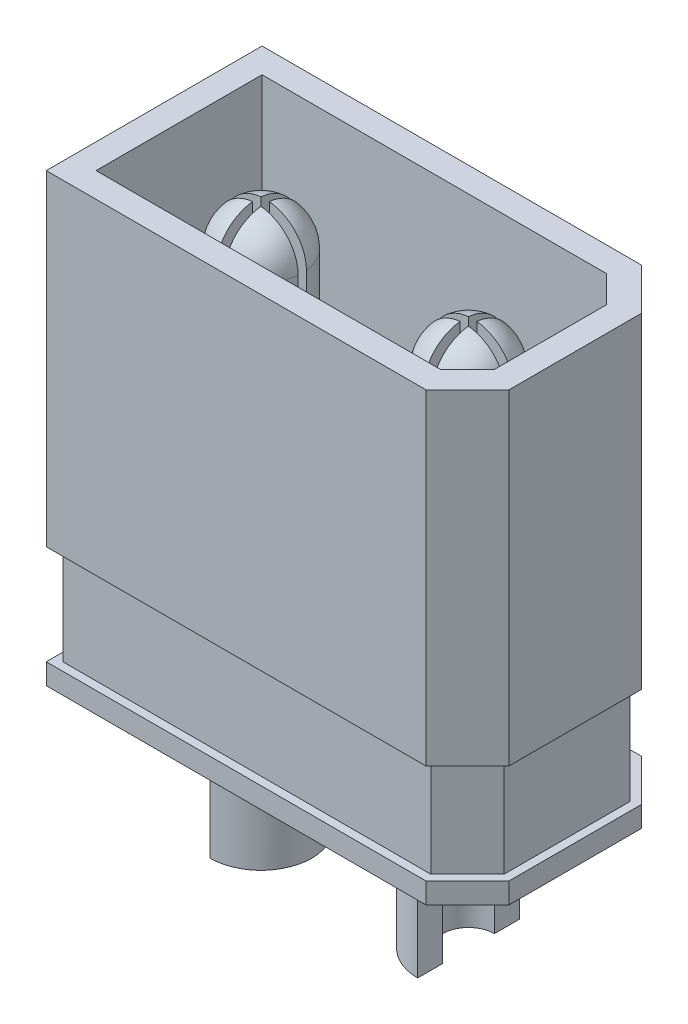
SolidWorks part; units mm, degrees
ref_plane "Front Plane" through (0, 0, 0) normal (0, 0, 1) x (1, 0, 0)
ref_plane "Top Plane" through (0, 0, 0) normal (0, 1, 0) x (1, 0, 0)
ref_plane "Right Plane" through (0, 0, 0) normal (1, 0, 0) x (0, 0, -1)
sketch "Sketch1" plane through (0, 0, 0) normal (0, 1, 0) x (1, 0, 0)
  line L0 (5.075, 1.6) -> (4.075, 2.6)
  line L1 (-5.075, 2.6) -> (5.075, 2.6)
  line L2 (-5.075, 2.6) -> (-5.075, -2.6)
  line L3 (-5.075, -2.6) -> (5.075, -2.6)
  line L4 (5.075, 2.6) -> (5.075, -2.6)
  line L5 (-5.075, 2.6) -> (5.075, -2.6) construction
  line L6 (-5.075, -2.6) -> (5.075, 2.6) construction
  line L7 (-5.075, 0) -> (5.075, 0) construction
  line L8 (5.075, -1.6) -> (4.075, -2.6)
  point P0 (0, 0)
  dimension "D1" = 5.2
  dimension "D2" = 10.15
  dimension "D3" = 1
  dimension "D4" = 45
extrude "Shape" add sketch "Sketch1" along normal blind 10.75 contours L8 L4 L0 L1 L2 L3 region at (-0.0916, 0, 0)
sketch "Sketch2" plane through (0, 10.75, 0) normal (0, 1, 0) x (1, 0, 0)
  line L12 (3.8265, -2) -> (4.475, -1.3515)
  line L13 (4.475, -1.3515) -> (4.475, 1.3515)
  line L14 (4.475, 1.3515) -> (3.8265, 2)
  line L15 (3.8265, 2) -> (-4.475, 2)
  line L16 (-4.475, 2) -> (-4.475, -2)
  line L17 (-4.475, -2) -> (3.8265, -2)
  line L18 (3.8265, -2) -> (4.475, -1.3515)
  line L19 (4.475, -1.3515) -> (4.475, 1.3515)
  line L20 (4.475, 1.3515) -> (3.8265, 2)
  line L21 (3.8265, 2) -> (-4.475, 2)
  line L22 (-4.475, 2) -> (-4.475, -2)
  line L23 (-4.475, -2) -> (3.8265, -2)
  dimension "D1" = 0.6
extrude "Cut-Extrude1" cut sketch "Sketch2" against normal blind 6.75
sketch "Sketch3" plane through (0, 4, 0) normal (0, 1, 0) x (1, 0, 0)
  line L0 (-4.475, 0) -> (4.475, 0) construction
  line L1 (-4.475, 2) -> (-4.475, -2) construction
  line L2 (4.475, -1.3515) -> (4.475, 1.3515) construction
  line L3 (0, 2) -> (0, -2) construction
  line L4 (3.8265, 2) -> (-4.475, 2) construction
  line L5 (-4.475, -2) -> (3.8265, -2) construction
  line L7 (1.6754, -1.6) -> (-1.6754, -1.6)
  line L8 (1.6754, -1.6) -> (1.6754, 1.6)
  line L9 (1.6754, 1.6) -> (-1.6754, 1.6)
  line L10 (-1.6754, -1.6) -> (-1.6754, 1.6)
  line L11 (1.6754, -1.6) -> (-1.6754, 1.6) construction
  line L12 (1.6754, 1.6) -> (-1.6754, -1.6) construction
  circle A0 centre (-2.5, 0) radius 1.8
  circle A1 centre (2.5, 0) radius 1.8
  point P15 (0, 0)
  dimension "D2" = 3.6
  dimension "D1" = 5
  dimension "D3" = 3.2
extrude "Cut-Extrude2" cut sketch "Sketch3" against normal up to next contours L7 A1 L9 A0 region at (0, 4, 0)
fillet "Fillet1" radius 0.2 4 edges at (-1.6754, 2, 1.6) (1.6754, 2, 1.6) (1.6754, 2, -1.6) (-1.6754, 2, -1.6)
sketch "Sketch4" plane through (0, 4, 0) normal (0, 1, 0) x (1, 0, 0)
  line L0 (0, 2) -> (0, -2) construction
  line L13 (-4.475, 2) -> (3.8265, 2) construction
  line L14 (-4.475, -2) -> (3.8265, -2) construction
  circle A0 centre (-2.5, 0) radius 1
  circle A2 centre (2.5, 0) radius 1
  dimension "D1" = 2
extrude "Boss-Extrude2" add sketch "Sketch4" along normal offset from surface (6.1 mm away) 0.65 contours A0 | A0 | A0 | A0 | A2 | A2 | A2 | A2 region at (-2.5, 4, 0) region at (2.5, 4, 0) up to face at (1.2755, 10.75, 0)
fillet "Fillet2" radius 1 2 edges at (2.5, 10.1, 1) (-2.5, 10.1, 1)
sketch "Sketch5" plane through (0, 10.75, 0) normal (0, 1, 0) x (1, 0, 0)
  line L0 (0, 2.6) -> (0, -2.6) construction
  line L1 (-2.6, 1) -> (-2.4, 1)
  line L2 (-2.6, 1) -> (-2.6, -1)
  line L3 (-2.6, -1) -> (-2.4, -1)
  line L4 (-2.4, 1) -> (-2.4, -1)
  line L5 (-2.6, 1) -> (-2.4, -1) construction
  line L6 (-2.6, -1) -> (-2.4, 1) construction
  line L7 (-1.5, 0.1) -> (-3.5, 0.1)
  line L8 (-1.5, 0.1) -> (-1.5, -0.1)
  line L9 (-1.5, -0.1) -> (-3.5, -0.1)
  line L10 (-3.5, 0.1) -> (-3.5, -0.1)
  line L11 (-1.5, 0.1) -> (-3.5, -0.1) construction
  line L12 (-1.5, -0.1) -> (-3.5, 0.1) construction
  line L13 (-5.075, 2.6) -> (4.075, 2.6) construction
  line L14 (-5.075, -2.6) -> (4.075, -2.6) construction
  line L15 (1.5, 0.1) -> (1.5, -0.1)
  line L16 (1.5, -0.1) -> (3.5, -0.1)
  line L17 (3.5, 0.1) -> (3.5, -0.1)
  line L18 (1.5, 0.1) -> (3.5, 0.1)
  line L19 (2.6, 1) -> (2.4, 1)
  line L20 (2.4, 1) -> (2.4, -1)
  line L21 (2.6, -1) -> (2.4, -1)
  line L22 (2.6, 1) -> (2.6, -1)
  circle A0 centre (-2.5, 0) radius 1 construction
  point P0 (-2.5, 0)
  point P8 (-2.5, 0)
  dimension "D1" = 0.2
extrude "Cut-Extrude3" cut sketch "Sketch5" against normal up to surface (6.75 mm away) contours L4 L3 L2 L1 | L7 L10 L9 L8 | L16 L17 L18 L15 | L20 L21 L22 L19 up to face at (2.5, 4, 1)
ref_plane "Plane1" through (0, 0.5, 0) normal (0, -1, 0) x (-1, 0, 0)
sketch "Sketch6" plane through (0, 0.5, 0) normal (0, -1, 0) x (-1, 0, 0)
  line L13 (-4.875, -1.5172) -> (-3.9922, -2.4)
  line L14 (-3.9922, -2.4) -> (4.875, -2.4)
  line L15 (4.875, -2.4) -> (4.875, 2.4)
  line L16 (4.875, 2.4) -> (-3.9922, 2.4)
  line L17 (-3.9922, 2.4) -> (-4.875, 1.5172)
  line L18 (-4.875, 1.5172) -> (-4.875, -1.5172)
  line L19 (-4.875, -1.5172) -> (-3.9922, -2.4)
  line L20 (-3.9922, -2.4) -> (4.875, -2.4)
  line L21 (4.875, -2.4) -> (4.875, 2.4)
  line L22 (4.875, 2.4) -> (-3.9922, 2.4)
  line L23 (-3.9922, 2.4) -> (-4.875, 1.5172)
  line L24 (-4.875, 1.5172) -> (-4.875, -1.5172)
  line L25 (-5.075, -1.6) -> (-4.075, -2.6)
  line L26 (-4.075, -2.6) -> (5.075, -2.6)
  line L27 (5.075, -2.6) -> (5.075, 2.6)
  line L28 (5.075, 2.6) -> (-4.075, 2.6)
  line L29 (-4.075, 2.6) -> (-5.075, 1.6)
  line L30 (-5.075, 1.6) -> (-5.075, -1.6)
  line L31 (-5.075, -1.6) -> (-4.075, -2.6)
  line L32 (-4.075, -2.6) -> (5.075, -2.6)
  line L33 (5.075, -2.6) -> (5.075, 2.6)
  line L34 (5.075, 2.6) -> (-4.075, 2.6)
  line L35 (-4.075, 2.6) -> (-5.075, 1.6)
  line L36 (-5.075, 1.6) -> (-5.075, -1.6)
  dimension "D1" = 0.2
  dimension "D2" = 0
extrude "Cut-Extrude4" cut sketch "Sketch6" against normal blind 2.4
sketch "Sketch8" plane through (0, 0, 0) normal (0, -1, 0) x (1, 0, 0)
  line L7 (-4.475, -2) -> (-4.475, 2) construction
  line L8 (3.8265, -2) -> (-4.475, -2) construction
  line L9 (4.475, -1.3515) -> (3.8265, -2) construction
  line L10 (4.475, 1.3515) -> (4.475, -1.3515) construction
  line L11 (3.8265, 2) -> (4.475, 1.3515) construction
  line L12 (-4.475, 2) -> (3.8265, 2) construction
  line L13 (-4.475, -2) -> (-4.475, 2)
  line L14 (3.8265, -2) -> (-4.475, -2)
  line L15 (4.475, -1.3515) -> (3.8265, -2)
  line L16 (4.475, 1.3515) -> (4.475, -1.3515)
  line L17 (3.8265, 2) -> (4.475, 1.3515)
  line L24 (-4.475, 2) -> (3.8265, 2)
extrude "Cut-Extrude5" cut sketch "Sketch8" against normal blind 1
sketch "Sketch7" plane through (0, 1, 0) normal (0, -1, 0) x (1, 0, 0)
  line L0 (0, 1.6) -> (0, -1.6) construction
  line L1 (-1.0717, 1.6) -> (1.0717, 1.6) construction
  line L2 (-1.0717, -1.6) -> (1.0717, -1.6) construction
  circle A0 centre (-2.5, 0) radius 1.225
  arc A1 (-2.4, -0.995) -> (-1.505, -0.1) centre (-2.5, 0) ccw construction
  circle A2 centre (-2.5, 0) radius 0.625
  circle A3 centre (2.5, 0) radius 0.625
  circle A4 centre (2.5, 0) radius 1.225
  dimension "D1" = 0.6
  dimension "D2" = 2.45
extrude "Boss-Extrude3" add sketch "Sketch7" along normal blind 4
sketch "Sketch9" plane through (0, -3, 0) normal (0, -1, 0) x (1, 0, 0)
  line L0 (0, 1.6) -> (0, -1.6) construction
  line L1 (-2.5, 1.225) -> (-3.725, 1.225)
  line L2 (-2.5, 1.225) -> (-2.5, -1.225)
  line L3 (-2.5, -1.225) -> (-3.725, -1.225)
  line L4 (-3.725, 1.225) -> (-3.725, -1.225)
  line L5 (-1.0717, 1.6) -> (1.0717, 1.6) construction
  line L6 (-1.0717, -1.6) -> (1.0717, -1.6) construction
  line L7 (-2.5, 1.225) -> (-2.5, -1.225) construction
  line L8 (2.5, 1.225) -> (3.725, 1.225)
  line L9 (2.5, 1.225) -> (2.5, -1.225)
  line L10 (2.5, -1.225) -> (3.725, -1.225)
  line L11 (3.725, 1.225) -> (3.725, -1.225)
  circle A0 centre (-2.5, 0) radius 1.225 construction
  circle A1 centre (-2.5, 0) radius 1.225 construction
extrude "Cut-Extrude6" cut sketch "Sketch9" against normal blind 2.3
